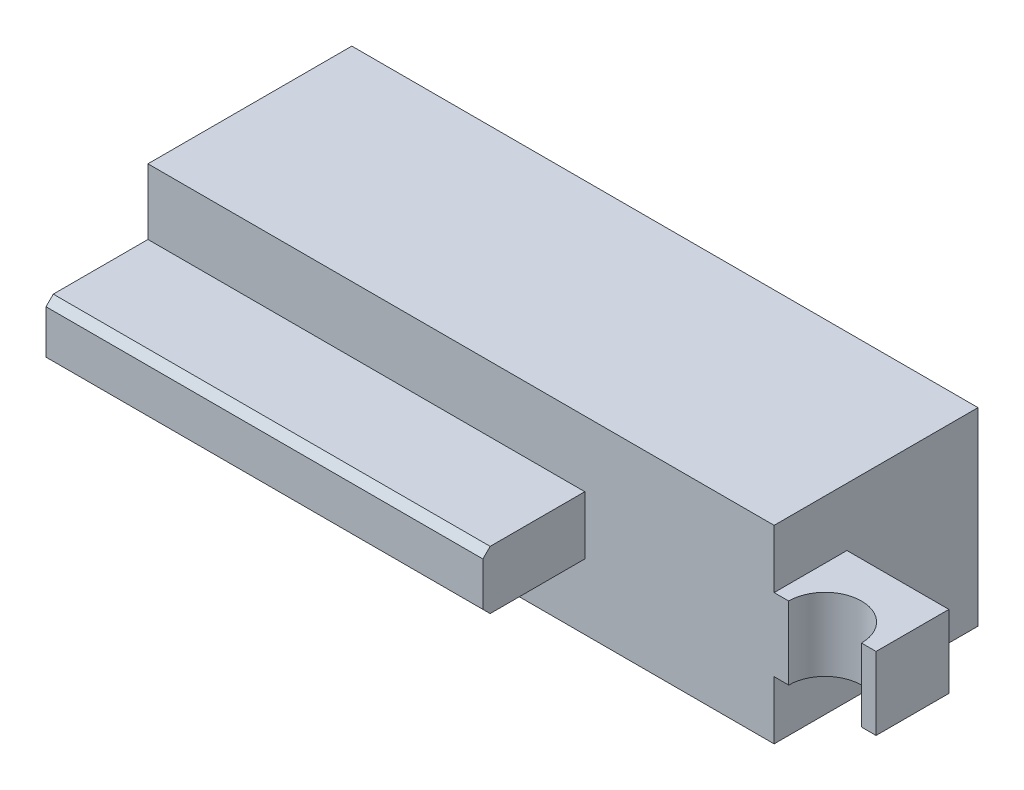
SolidWorks part; units mm, degrees
ref_plane "前视基准面" through (0, 0, 0) normal (0, 0, 1) x (1, 0, 0)
ref_plane "上视基准面" through (0, 0, 0) normal (0, 1, 0) x (1, 0, 0)
ref_plane "右视基准面" through (0, 0, 0) normal (1, 0, 0) x (0, 0, -1)
sketch "草图1" plane through (0, 0, 0) normal (1, 0, 0) x (0, 0, -1)
  line L0 (-15.5739, 0) -> (17.5206, 0) construction
  line L1 (0, 0) -> (0, 24.6123) construction
  line L2 (0, 0) -> (25, 0)
  line L3 (25, 0) -> (25, 17)
  line L4 (25, 17) -> (0, 17)
  line L5 (0, 17) -> (0, 0)
extrude "凸台-拉伸1" add sketch "草图1" along normal blind 50
sketch "草图2" plane through (0, 0, 0) normal (-1, 0, 0) x (0, 0, 1)
  line L0 (0, 17) -> (0, 11)
  line L1 (0, 17) -> (0, 0) construction
  line L2 (0, 11) -> (-11, 11)
  line L3 (-11, 11) -> (-11, 17)
  line L4 (-25, 17) -> (0, 17) construction
  line L5 (-11, 17) -> (0, 17)
  line L6 (-25, 8.5) -> (0, 8.5) construction
  line L7 (-25, 0) -> (-25, 17) construction
  line L8 (-11, 6) -> (-11, 0)
  line L9 (0, 6) -> (-11, 6)
  line L10 (0, 0) -> (0, 6)
  line L11 (-11, 0) -> (0, 0)
extrude "切除-拉伸1" cut sketch "草图2" against normal blind 50 contours L5 L0 L2 L3 | L8 L11 L10 L9
sketch "草图3" plane through (0, 11, 0) normal (0, 1, 0) x (1, 0, 0)
  line L0 (50, 0) -> (50, 11)
  line L1 (50, 11) -> (30, 11)
  line L2 (50, 11) -> (0, 11) construction
  line L3 (30, 11) -> (30, 0)
  line L4 (50, 0) -> (0, 0) construction
  line L5 (30, 0) -> (50, 0)
extrude "切除-拉伸2" cut sketch "草图3" against normal blind 50
sketch "草图4" plane through (0, 0, -25) normal (0, 0, -1) x (-1, 0, 0)
  line L0 (-50, 8.5) -> (0, 8.5) construction
  line L1 (-50, 0) -> (-50, 17) construction
  line L2 (0, 0) -> (0, 17) construction
  line L4 (-50, 11) -> (-43, 11)
  line L5 (-43, 11) -> (-43, 17)
  line L6 (-50, 17) -> (0, 17) construction
  line L7 (-43, 17) -> (-50, 17)
  line L8 (-50, 17) -> (-50, 11)
  line L9 (-50, 0) -> (-50, 6)
  line L10 (-43, 0) -> (-50, 0)
  line L11 (-43, 6) -> (-43, 0)
  line L12 (-50, 6) -> (-43, 6)
extrude "切除-拉伸3" cut sketch "草图4" against normal blind 50
sketch "草图5" plane through (0, 11, 0) normal (0, 1, 0) x (1, 0, 0)
  line L1 (50, 11) -> (50, 25) construction
  line L2 (50, 16) -> (43, 16)
  line L3 (43, 11) -> (43, 25) construction
  line L4 (43, 16) -> (43, 25)
  line L5 (43, 25) -> (50, 25)
  line L6 (50, 25) -> (50, 16)
extrude "切除-拉伸4" cut sketch "草图5" against normal blind 50 contours L2 L4 L5 L6
sketch "草图6" plane through (0, 11, 0) normal (0, 1, 0) x (1, 0, 0)
  line L0 (43, 11) -> (50, 11) construction
  circle A0 centre (46.5, 11) radius 2.5
extrude "切除-拉伸5" cut sketch "草图6" against normal blind 50
sketch "草图7" plane through (0, 0, 0) normal (-1, 0, 0) x (0, 0, 1)
  line L0 (0, 8.5) -> (-25, 8.5)
  line L1 (0, 11) -> (0, 6) construction
  line L2 (-25, 0) -> (-25, 17) construction
  line L3 (-25, 17) -> (-25, 15)
  line L4 (-25, 15) -> (-11, 15)
  line L5 (-11, 11) -> (-11, 17) construction
  line L6 (-11, 15) -> (-11, 17)
  line L7 (-11, 17) -> (-25, 17)
  line L8 (-11, 2) -> (-11, 0)
  line L9 (-25, 2) -> (-11, 2)
  line L10 (-25, 0) -> (-25, 2)
  line L11 (-11, 0) -> (-25, 0)
  line M6 (-11, 11) -> (-11, 17)
  line M7 (-11, 17) -> (-25, 17)
  line M8 (-25, 17) -> (-25, 0)
  line M9 (-25, 0) -> (-11, 0)
  line M10 (-11, 0) -> (-11, 6)
extrude "切除-拉伸8" cut sketch "草图7" against normal blind 50 contours L4 M8 M6 M7 | L9 M8 M9 M10 region at (0, 16, -18) region at (0, 1, -18)
sketch "草图10" plane through (0, 0, 0) normal (-1, 0, 0) x (0, 0, 1)
  line L0 (0, 11) -> (-4, 11)
  line L1 (0, 11) -> (-11, 11) construction
  line L2 (-4, 11) -> (-4, 6)
  line L3 (0, 6) -> (-11, 6) construction
  line L4 (-4, 6) -> (0, 6)
  line L5 (0, 6) -> (0, 11)
extrude "切除-拉伸9" cut sketch "草图10" against normal blind 50
sketch "草图11" plane through (0, 0, 0) normal (-1, 0, 0) x (0, 0, 1)
  line L0 (-22, 12) -> (-22, 5)
  line L3 (-22, 12) -> (-14, 12)
  line L4 (-14, 12) -> (-14, 5)
  line L5 (-14, 5) -> (-22, 5)
extrude "切除-拉伸10" cut sketch "草图11" against normal blind 30
sketch "草图12" plane through (0, 0, 0) normal (-1, 0, 0) x (0, 0, 1)
  line L0 (-4, 8.5) -> (-25, 8.5) construction
  line L1 (-4, 11) -> (-4, 6) construction
  line L2 (-25, 2) -> (-25, 15) construction
  line L3 (-4, 11) -> (-4, 10)
  line L4 (-4, 11) -> (-5, 11)
  line L5 (-4, 11) -> (-11, 11) construction
  line L6 (-5, 11) -> (-4, 10)
  line L7 (-4, 6) -> (-5, 6)
  line L8 (-4, 6) -> (-4, 7)
  line L9 (-5, 6) -> (-4, 7)
extrude "切除-拉伸11" cut sketch "草图12" against normal blind 50 contours L6 L3 L4 | L7 L9 L8
sketch "草图13" plane through (0, 0, 0) normal (-1, 0, 0) x (0, 0, 1)
  line L0 (-11, 11) -> (-11, 10.5)
  line L1 (-11, 10.5) -> (-4.5, 10.5)
  line L2 (-5, 11) -> (-4, 10) construction
  line L3 (-4.5, 10.5) -> (-5, 11)
  line L4 (-5, 11) -> (-11, 11)
  line L5 (-4, 8.5) -> (-25, 8.5) construction
  line L6 (-4, 10) -> (-4, 7) construction
  line L7 (-25, 2) -> (-25, 15) construction
  line L8 (-4.5, 6.5) -> (-5, 6)
  line L9 (-11, 6.5) -> (-4.5, 6.5)
  line L10 (-11, 6) -> (-11, 6.5)
  line L11 (-5, 6) -> (-11, 6)
extrude "切除-拉伸12" cut sketch "草图13" against normal blind 50
sketch "草图14" plane through (0, 0, -25) normal (0, 0, -1) x (-1, 0, 0)
  circle A0 centre (-3, 8.5) radius 1.55
  circle A1 centre (-11, 8.5) radius 1.55
extrude "切除-拉伸13" cut sketch "草图14" against normal blind 5 contours A0 | A1 | A1 region at (3, 8.5, -25) region at (11, 8.5, -25)
